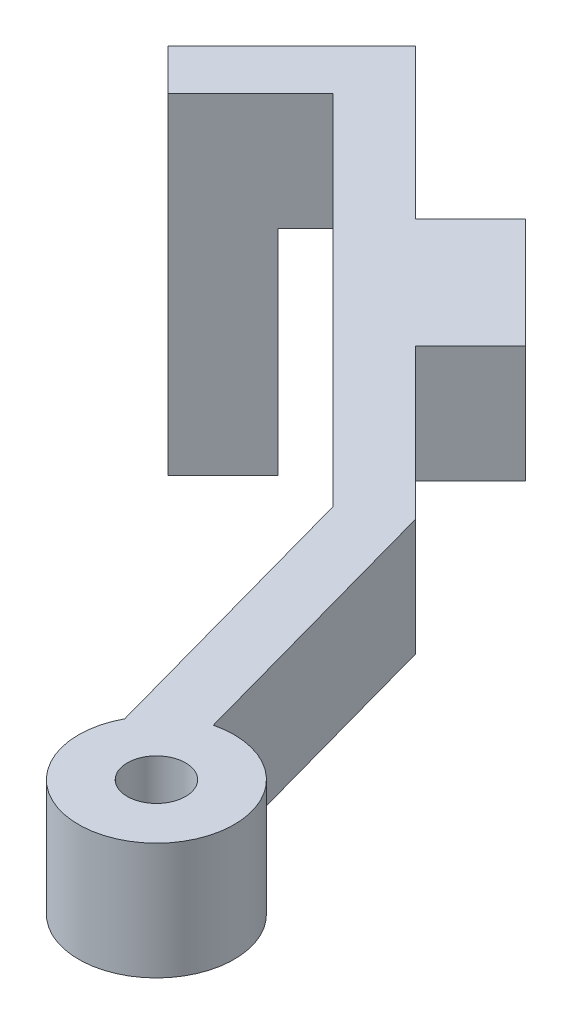
SolidWorks part; units mm, degrees
ref_plane "Front Plane" through (0, 0, 0) normal (0, 0, 1) x (1, 0, 0)
ref_plane "Top Plane" through (0, 0, 0) normal (0, 1, 0) x (1, 0, 0)
ref_plane "Right Plane" through (0, 0, 0) normal (1, 0, 0) x (0, 0, -1)
sketch "Sketch1" plane through (0, 0, 0) normal (0, 1, 0) x (1, 0, 0)
  circle A3 centre (0, -38.254) radius 38.254 construction
  circle A4 centre (0, -40.254) radius 40.254 construction
  circle A5 centre (0, -45.254) radius 45.254 construction
  dimension "D1" = 90.508
  dimension "D2" = 80.508
  dimension "D3" = 76.508
sketch "Sketch3" plane through (0, 0, 0) normal (0, 1, 0) x (1, 0, 0)
  line L8 (58.3717, -39.6268) -> (0, 18.7448)
  line L9 (0, 18.7448) -> (-58.3717, -39.6268)
  line L10 (-58.3717, -39.6268) -> (58.3717, -39.6268) construction
  line L17 (58.3717, -39.6268) -> (73.025, -92.6112)
  line L23 (73.025, -92.6112) -> (82.55, -92.6112)
  line L25 (66.8826, -34.6674) -> (80.2733, -83.0862)
  line L26 (66.8826, -34.6674) -> (0, 32.2152)
  line L27 (0, 32.2152) -> (-65.1069, -32.8917)
  line L28 (-65.1069, -32.8917) -> (-58.3717, -39.6268)
  line L30 (80.2733, -83.0862) -> (82.55, -83.0862) construction
  line L31 (80.2733, -83.0862) -> (82.55, -92.6112)
  line L32 (-20.2056, 12.0096) -> (-13.4704, 5.2744)
  circle A3 centre (0, -45.254) radius 45.254 construction
  dimension "D1" = 45
  dimension "D2" = 45
  dimension "D4" = 52.9844
  dimension "D5" = 9.525
  dimension "D7" = 82.55
  dimension "D3" = 82.55
  dimension "D8" = 63.5
  dimension "D6" = 9.525
extrude "Boss-Extrude1" add sketch "Sketch3" along normal blind 19.05 from offset 44.45 contours L27 L32 L9 L8 L17 L23 L31 L25 L26 region at (30.3291, 0, 9.2978)
sketch "Sketch26" plane through (0, 63.5, 0) normal (0, 1, 0) x (1, 0, 0)
  circle A0 centre (82.55, -92.6112) radius 12.7
  circle A1 centre (82.55, -92.6112) radius 4.7625
  point P4 (82.55, -92.6112)
  line M11 (73.025, -92.6112) -> (82.55, -92.6112)
  line M12 (82.55, -92.6112) -> (80.2733, -83.0862)
  dimension "D1" = 25.4
  dimension "D2" = 9.525
extrude "Boss-Extrude7" add sketch "Sketch26" against normal up to surface (19.05 mm away) contours A0 up to face at (36.3807, 44.45, 30.4843)
extrude "Cut-Extrude6" cut sketch "Sketch26<3>" against normal through all contours A1 M11 M12 | A1 M12 M11 region at (83.1742, 63.5, 93.1038) region at (80.2389, 63.5, 90.7875)
sketch "Sketch26<3>" plane through (0, 63.5, 0) normal (0, 1, 0) x (1, 0, 0) same geometry as "Sketch26"
sketch "Sketch28" plane through (0, 44.45, 0) normal (0, -1, 0) x (1, 0, 0)
  line L0 (-4.4901, -14.2547) -> (-11.2253, -20.9899)
  line L1 (0, -32.2152) -> (-20.2056, -12.0096) construction
  line L2 (-11.2253, -20.9899) -> (-20.2056, -12.0096)
  line L3 (-20.2056, -12.0096) -> (-13.4704, -5.2744)
  line L4 (-13.4704, -5.2744) -> (-4.4901, -14.2547)
  dimension "D1" = 12.7
extrude "Boss-Extrude8" add sketch "Sketch28" along normal blind 34.925
sketch "Sketch29" plane through (0, 63.5, 0) normal (0, 1, 0) x (1, 0, 0)
  line L0 (42.4216, -10.2064) -> (51.4018, -1.2261)
  line L1 (66.8826, -34.6674) -> (0, 32.2152) construction
  line L2 (51.4018, -1.2261) -> (33.4413, 16.7344)
  line L3 (33.4413, 16.7344) -> (24.4611, 7.7541)
  line L4 (24.4611, 7.7541) -> (42.4216, -10.2064)
  point P4 (33.4413, -1.2261)
  dimension "D1" = 25.4
  dimension "D2" = 12.7
extrude "Boss-Extrude9" add sketch "Sketch29" against normal up to surface (19.05 mm away) up to face at (82.55, 44.45, 97.3737)
equation "\"tightTol\"= 0.005in"
equation "\"normTol\"= 0.01in"
equation "\"looseTol\"= 0.02in"
equation "\"D1@Sketch1\"=\"looseTol\"+9cm"
equation "\"D2@Sketch1\"=8cm+\"looseTol\""
equation "\"D3@Sketch1\"=7.6cm+\"looseTol\""
equation "\"D2\"= 0.875 - 10.7mm"
equation "\"D1\"= 10.7mm"
equation "\"D1@Boss-Extrude1\"=40mm"
equation "\"D19@Boss-Extrude2\"=0.250000-1.5*\"normTol\""
equation "\"D4@Sketch3\"= 4.95 - 2.864"
